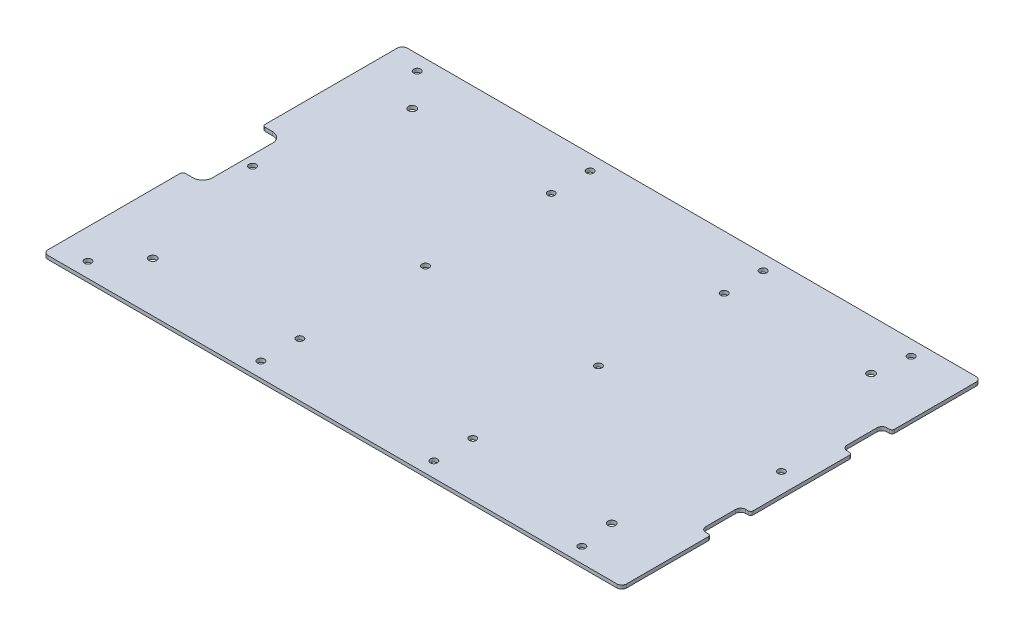
SolidWorks part; units mm, degrees
material "1060 Alloy"
ref_plane "Front" through (0, 0, 0) normal (0, 0, 1) x (1, 0, 0)
ref_plane "Top" through (0, 0, 0) normal (0, 1, 0) x (1, 0, 0)
ref_plane "Right" through (0, 0, 0) normal (1, 0, 0) x (0, 0, -1)
sketch "Sketch1" plane through (0, 0, 0) normal (0, 1, 0) x (1, 0, 0)
  line L0 (-55.0333, 0) -> (-165.1, 0) construction
  line L1 (-180.975, 114.3) -> (180.975, 114.3)
  line L2 (-184.15, 111.125) -> (-184.15, -111.125)
  line L3 (-180.975, -114.3) -> (180.975, -114.3)
  line L4 (184.15, 111.125) -> (184.15, -111.125)
  line L5 (-184.15, 114.3) -> (184.15, -114.3) construction
  line L6 (-184.15, -114.3) -> (184.15, 114.3) construction
  line L7 (-165.1, -104.775) -> (165.1, -104.775) construction
  line L8 (-165.1, -104.775) -> (-165.1, 104.775) construction
  line L9 (-165.1, 104.775) -> (165.1, 104.775) construction
  line L10 (165.1, -104.775) -> (165.1, 104.775) construction
  line L11 (-165.1, -104.775) -> (165.1, 104.775) construction
  line L12 (-165.1, 104.775) -> (165.1, -104.775) construction
  line L13 (-55.0333, -104.775) -> (55.0333, -104.775) construction
  line L14 (-55.0333, -104.775) -> (-55.0333, 104.775) construction
  line L15 (-55.0333, 104.775) -> (55.0333, 104.775) construction
  line L16 (55.0333, -104.775) -> (55.0333, 104.775) construction
  line L17 (-55.0333, -104.775) -> (55.0333, 104.775) construction
  line L18 (-55.0333, 104.775) -> (55.0333, -104.775) construction
  line L19 (55.0333, 0) -> (165.1, 0) construction
  line L20 (-55.0333, 0) -> (55.0333, 0) construction
  line L31 (-55.0291, 80.01) -> (55.0291, 80.01) construction
  line L32 (149.225, -104.775) -> (149.225, 104.775) construction
  line L33 (-55.0291, 80.01) -> (-55.0291, -80.01) construction
  line L34 (-55.0291, -80.01) -> (55.0291, -80.01) construction
  line L35 (55.0291, 80.01) -> (55.0291, -80.01) construction
  line L36 (-55.0291, 80.01) -> (55.0291, -80.01) construction
  line L37 (-55.0291, -80.01) -> (55.0291, 80.01) construction
  circle A0 centre (-165.1, 104.775) radius 2.2479
  circle A1 centre (-55.0333, 104.775) radius 2.2479
  circle A2 centre (55.0333, 104.775) radius 2.2479
  circle A3 centre (165.1, 104.775) radius 2.2479 construction
  circle A4 centre (165.1, -104.775) radius 2.2479 construction
  circle A5 centre (55.0333, -104.775) radius 2.2479
  circle A6 centre (-55.0333, -104.775) radius 2.2479
  circle A7 centre (-165.1, -104.775) radius 2.2479
  circle A12 centre (-55.0333, 0) radius 2.2479
  circle A13 centre (55.0333, 0) radius 2.2479
  arc A14 (184.15, 111.125) -> (180.975, 114.3) centre (180.975, 111.125) ccw
  arc A15 (184.15, -111.125) -> (180.975, -114.3) centre (180.975, -111.125) cw
  arc A16 (-180.975, -114.3) -> (-184.15, -111.125) centre (-180.975, -111.125) cw
  arc A17 (-180.975, 114.3) -> (-184.15, 111.125) centre (-180.975, 111.125) ccw
  circle A24 centre (149.225, -104.775) radius 2.2479
  circle A25 centre (149.225, 104.775) radius 2.2479
  circle A26 centre (55.0291, -80.01) radius 2.2479
  circle A27 centre (-55.0291, -80.01) radius 2.2479
  circle A28 centre (-55.0291, 80.01) radius 2.2479
  circle A29 centre (55.0291, 80.01) radius 2.2479
  circle A30 centre (171.45, 0) radius 2.2479
  circle A31 centre (-165.1, 0) radius 2.2479
  circle A32 centre (-146.05, 82.55) radius 2.4574 construction
  circle A33 centre (-146.05, 82.55) radius 2.4575
  circle A34 centre (146.05, 82.55) radius 2.4574 construction
  circle A35 centre (146.05, 82.55) radius 2.4575
  circle A36 centre (-146.05, -82.55) radius 2.4574 construction
  circle A37 centre (-146.05, -82.55) radius 2.4575
  circle A38 centre (146.05, -82.55) radius 2.4574 construction
  circle A39 centre (146.05, -82.55) radius 2.4575
  point P0 (0, 0)
  point P6 (0, 0)
  point P11 (0, 0)
  point P28 (0, 0)
  point P29 (0, 0)
  point P32 (0, 0)
  dimension "D5" = 4.4958
  dimension "D8" = 4.4958
  dimension "D11" = 3.175
  dimension "D10" = 12.7
  dimension "D12" = 19.05
  dimension "D13" = 110.0667
  dimension "D1" = 368.3
  dimension "D2" = 228.6
  dimension "D3" = 9.525
  dimension "D4" = 19.05
  dimension "D6" = 160.02
  dimension "D7" = 34.925
  dimension "D9" = 110.0582
extrude "Boss-Extrude1" add sketch "Sketch1" along normal blind 2.286
sketch "Sketch2" plane through (0, 0, 0) normal (0, -1, 0) x (1, 0, 0)
  line L5 (184.15, 111.125) -> (184.15, -111.125) construction
  line L6 (184.15, 57.658) -> (180.975, 57.658)
  line L7 (184.15, 57.658) -> (184.15, 32.258)
  line L8 (184.15, 32.258) -> (180.975, 32.258)
  line L9 (177.8, 54.483) -> (177.8, 35.433)
  line L10 (-184.15, 0) -> (188.1505, 0) construction
  line L11 (-184.15, -111.125) -> (-184.15, 111.125) construction
  line L12 (188.1505, -117.475) -> (188.1505, 117.475) construction
  line L13 (177.8, 44.958) -> (184.15, 44.958) construction
  line L14 (184.15, -32.258) -> (180.975, -32.258)
  line L15 (184.15, -57.658) -> (184.15, -32.258)
  line L16 (177.8, -54.483) -> (177.8, -35.433)
  line L17 (184.15, -57.658) -> (180.975, -57.658)
  line L19 (-184.15, 25.4) -> (-177.8, 25.4)
  line L20 (-184.15, 25.4) -> (-184.15, -25.4)
  line L21 (-184.15, -25.4) -> (-177.8, -25.4)
  line L22 (-171.45, 19.05) -> (-171.45, -19.05)
  arc A0 (180.975, -57.658) -> (177.8, -54.483) centre (180.975, -54.483) cw
  arc A1 (177.8, -35.433) -> (180.975, -32.258) centre (180.975, -35.433) cw
  arc A2 (177.8, 35.433) -> (180.975, 32.258) centre (180.975, 35.433) ccw
  arc A3 (177.8, 54.483) -> (180.975, 57.658) centre (180.975, 54.483) cw
  arc A4 (-171.45, -19.05) -> (-177.8, -25.4) centre (-177.8, -19.05) cw
  arc A5 (-171.45, 19.05) -> (-177.8, 25.4) centre (-177.8, 19.05) ccw
  point P20 (177.8, -57.658)
  point P23 (177.8, -32.258)
  point P26 (177.8, 32.258)
  point P29 (177.8, 57.658)
  point P38 (-171.45, 25.4)
  dimension "D4" = 3.175
  dimension "D7" = 6.35
  dimension "D1" = 25.4
  dimension "D2" = 44.958
  dimension "D3" = 6.35
  dimension "D5" = 50.8
  dimension "D6" = 12.7
extrude "Cut-Extrude1" cut sketch "Sketch2" against normal through all
fillet "Fillet1" radius 1.5875 6 edges at (184.15, 1.143, -57.658) (184.15, 1.143, -32.258) (184.15, 1.143, 32.258) (184.15, 1.143, 57.658) (-184.15, 1.143, -25.4) (-184.15, 1.143, 25.4)
sketch "Sketch3" plane through (0, 2.286, 0) normal (0, 1, 0) x (1, 0, 0)
  line L0 (-198.0256, -111.0509) -> (-198.0256, 117.5491)
  line L1 (204.2781, -126.2696) -> (-1014.9219, -126.2696)
  line L2 (204.2781, -126.2696) -> (204.2781, 1092.9304)
  line L3 (204.2781, 1092.9304) -> (-1014.9219, 1092.9304)
  line L4 (-1014.9219, -126.2696) -> (-1014.9219, 1092.9304)
  line L5 (182.9744, -111.0509) -> (-185.3256, -111.0509)
  line L6 (182.9744, -111.0509) -> (182.9744, 117.5491)
  line L7 (182.9744, 117.5491) -> (-185.3256, 117.5491)
  line L8 (-185.3256, -111.0509) -> (-185.3256, 117.5491)
  line L9 (-198.0256, -111.0509) -> (-566.3256, -111.0509)
  line L10 (-566.3256, -111.0509) -> (-566.3256, 117.5491)
  line L11 (-198.0256, 117.5491) -> (-566.3256, 117.5491)
  line L12 (-579.0256, -111.0509) -> (-579.0256, 117.5491)
  line L13 (-579.0256, -111.0509) -> (-947.3256, -111.0509)
  line L14 (-947.3256, -111.0509) -> (-947.3256, 117.5491)
  line L15 (-579.0256, 117.5491) -> (-947.3256, 117.5491)
  line L16 (-198.0256, 130.2491) -> (-198.0256, 358.8491)
  line L17 (-198.0256, 130.2491) -> (-566.3256, 130.2491)
  line L18 (-566.3256, 130.2491) -> (-566.3256, 358.8491)
  line L19 (-198.0256, 358.8491) -> (-566.3256, 358.8491)
  line L20 (-579.0256, 130.2491) -> (-579.0256, 358.8491)
  line L21 (-579.0256, 130.2491) -> (-947.3256, 130.2491)
  line L22 (-947.3256, 130.2491) -> (-947.3256, 358.8491)
  line L23 (-579.0256, 358.8491) -> (-947.3256, 358.8491)
  line L24 (-198.0256, 371.5491) -> (-198.0256, 600.1491)
  line L25 (-198.0256, 371.5491) -> (-566.3256, 371.5491)
  line L26 (-566.3256, 371.5491) -> (-566.3256, 600.1491)
  line L27 (-198.0256, 600.1491) -> (-566.3256, 600.1491)
  line L28 (-579.0256, 371.5491) -> (-579.0256, 600.1491)
  line L29 (-579.0256, 371.5491) -> (-947.3256, 371.5491)
  line L30 (-947.3256, 371.5491) -> (-947.3256, 600.1491)
  line L31 (-579.0256, 600.1491) -> (-947.3256, 600.1491)
  line L32 (-198.0256, 612.8491) -> (-198.0256, 841.4491)
  line L33 (-198.0256, 612.8491) -> (-566.3256, 612.8491)
  line L34 (-566.3256, 612.8491) -> (-566.3256, 841.4491)
  line L35 (-198.0256, 841.4491) -> (-566.3256, 841.4491)
  line L36 (-579.0256, 612.8491) -> (-579.0256, 841.4491)
  line L37 (-579.0256, 612.8491) -> (-947.3256, 612.8491)
  line L38 (-947.3256, 612.8491) -> (-947.3256, 841.4491)
  line L39 (-579.0256, 841.4491) -> (-947.3256, 841.4491)
  line L40 (-198.0256, 854.1491) -> (-198.0256, 1082.7491)
  line L41 (-198.0256, 854.1491) -> (-566.3256, 854.1491)
  line L42 (-566.3256, 854.1491) -> (-566.3256, 1082.7491)
  line L43 (-198.0256, 1082.7491) -> (-566.3256, 1082.7491)
  line L44 (-579.0256, 854.1491) -> (-579.0256, 1082.7491)
  line L45 (-579.0256, 854.1491) -> (-947.3256, 854.1491)
  line L46 (-947.3256, 854.1491) -> (-947.3256, 1082.7491)
  line L47 (-579.0256, 1082.7491) -> (-947.3256, 1082.7491)
  line L48 (182.9744, 130.2491) -> (182.9744, 358.8491)
  line L49 (182.9744, 130.2491) -> (-185.3256, 130.2491)
  line L50 (-185.3256, 130.2491) -> (-185.3256, 358.8491)
  line L51 (182.9744, 358.8491) -> (-185.3256, 358.8491)
  line L52 (182.9744, 371.5491) -> (182.9744, 600.1491)
  line L53 (182.9744, 371.5491) -> (-185.3256, 371.5491)
  line L54 (-185.3256, 371.5491) -> (-185.3256, 600.1491)
  line L55 (182.9744, 600.1491) -> (-185.3256, 600.1491)
  line L56 (182.9744, 612.8491) -> (182.9744, 841.4491)
  line L57 (182.9744, 612.8491) -> (-185.3256, 612.8491)
  line L58 (-185.3256, 612.8491) -> (-185.3256, 841.4491)
  line L59 (182.9744, 841.4491) -> (-185.3256, 841.4491)
  line L60 (182.9744, 854.1491) -> (182.9744, 1082.7491)
  line L61 (182.9744, 854.1491) -> (-185.3256, 854.1491)
  line L62 (-185.3256, 854.1491) -> (-185.3256, 1082.7491)
  line L63 (182.9744, 1082.7491) -> (-185.3256, 1082.7491)
  dimension "D1" = 1219.2
  dimension "D2" = 1219.2
  dimension "D3" = 368.3
  dimension "D4" = 228.6
  dimension "D5" = 3
  dimension "D6" = 5
